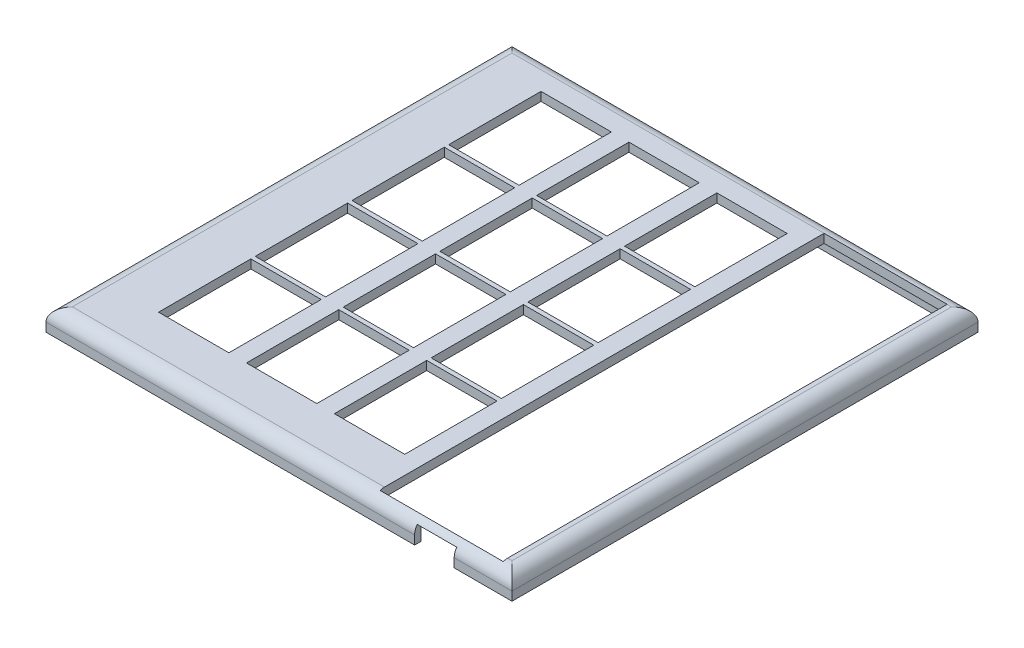
SolidWorks part; units mm, degrees
ref_plane "Front Plane" through (0, 0, 0) normal (0, 0, 1) x (1, 0, 0)
ref_plane "Top Plane" through (0, 0, 0) normal (0, 1, 0) x (1, 0, 0)
ref_plane "Right Plane" through (0, 0, 0) normal (1, 0, 0) x (0, 0, -1)
sketch "Sketch2" plane through (0, 0, 0) normal (0, 1, 0) x (1, 0, 0)
  line L2 (-4.4726, 8.8449) -> (101.5274, 8.8449)
  line L3 (-4.4726, 8.8449) -> (-4.4726, -97.1551)
  line L4 (-4.4726, -97.1551) -> (101.5274, -97.1551)
  line L5 (101.5274, 8.8449) -> (101.5274, -97.1551)
  line L6 (-4.4726, 8.8449) -> (101.5274, -97.1551) construction
  line L7 (-4.4726, -97.1551) -> (101.5274, 8.8449) construction
  dimension "D1" = 106
  dimension "D2" = 106
extrude "Boss-Extrude3" add sketch "Sketch2" along normal blind 5
sketch "Sketch3" plane through (0, 0, 0) normal (0, 1, 0) x (1, 0, 0)
  line L0 (-4.4726, -97.1551) -> (101.5274, 8.8449) construction
  line L1 (-2.9726, 7.3449) -> (100.0274, 7.3449)
  line L2 (-2.9726, 7.3449) -> (-2.9726, -95.6551)
  line L3 (-2.9726, -95.6551) -> (100.0274, -95.6551)
  line L4 (100.0274, 7.3449) -> (100.0274, -95.6551)
  line L5 (-2.9726, 7.3449) -> (100.0274, -95.6551) construction
  line L6 (-2.9726, -95.6551) -> (100.0274, 7.3449) construction
  line L7 (-4.4726, 8.8449) -> (101.5274, -97.1551) construction
  point P0 (48.5274, -44.1551)
  dimension "D1" = 103
  dimension "D2" = 103
extrude "Cut-Extrude1" cut sketch "Sketch3" along normal blind 3
sketch "Sketch4" plane through (0, 0, 97.1551) normal (0, 0, 1) x (1, 0, 0)
  line L0 (-4.4726, 0) -> (101.5274, 0) construction
  line L1 (79.3774, 3.7843) -> (88.3774, 3.7843)
  line L2 (79.3774, 3.7843) -> (79.3774, 0)
  line L3 (79.3774, 0) -> (88.3774, 0)
  line L4 (88.3774, 3.7843) -> (88.3774, 0)
  line L7 (101.5274, 5) -> (101.5274, 0) construction
  dimension "D1" = 9
  dimension "D2" = 13.15
extrude "Cut-Extrude2" cut sketch "Sketch4" against normal blind 10
fillet "Fillet1" radius 3 4 edges at (101.5274, 5, 44.1551) (48.5274, 5, 97.1551) (48.5274, 5, -8.8449) (-4.4726, 5, 44.1551)
sketch "Sketch5" plane through (0, 5, 0) normal (0, 1, 0) x (1, 0, 0)
  line L1 (69.5274, -95.1551) -> (97.5274, -95.1551)
  line L2 (69.5274, -95.1551) -> (69.5274, 5.8449)
  line L3 (69.5274, 5.8449) -> (97.5274, 5.8449)
  line L4 (97.5274, -95.1551) -> (97.5274, 5.8449)
  line L5 (101.5274, 8.8449) -> (101.5274, -97.1551) construction
  line L7 (-4.4726, -97.1551) -> (101.5274, -97.1551) construction
  dimension "D1" = 28
  dimension "D2" = 101
  dimension "D3" = 4
  dimension "D4" = 2
extrude "Cut-Extrude3" cut sketch "Sketch5" against normal blind 10
ref_plane "Plane1" through (0, 5, 0) normal (0, 1, 0) x (1, 0, 0)
sketch "Sketch6" plane through (0, 5, 0) normal (0, 1, 0) x (1, 0, 0)
  line L2 (49.3774, -69.4051) -> (49.3774, -85.4051)
  line L3 (49.3774, -85.4051) -> (65.3774, -85.4051)
  line L4 (65.3774, -69.4051) -> (65.3774, -85.4051)
  line L5 (49.3774, -69.4051) -> (65.3774, -85.4051) construction
  line L6 (49.3774, -85.4051) -> (65.3774, -69.4051) construction
  line L8 (65.3774, -69.4051) -> (65.3774, -64.4051)
  line L9 (65.3774, -64.4051) -> (49.3774, -64.4051)
  line L10 (49.3774, -69.4051) -> (49.3774, -64.4051)
  point P0 (57.3774, -77.4051)
  dimension "D1" = 16
  dimension "D2" = 16
  dimension "D3" = 5
extrude "Cut-Extrude5" cut sketch "Sketch6" against normal blind 2
pattern_linear "LPattern1" count 4 spacing 22 along (0, 0, -1) count 3 spacing 20 along (-1, 0, 0) of "Cut-Extrude5"
